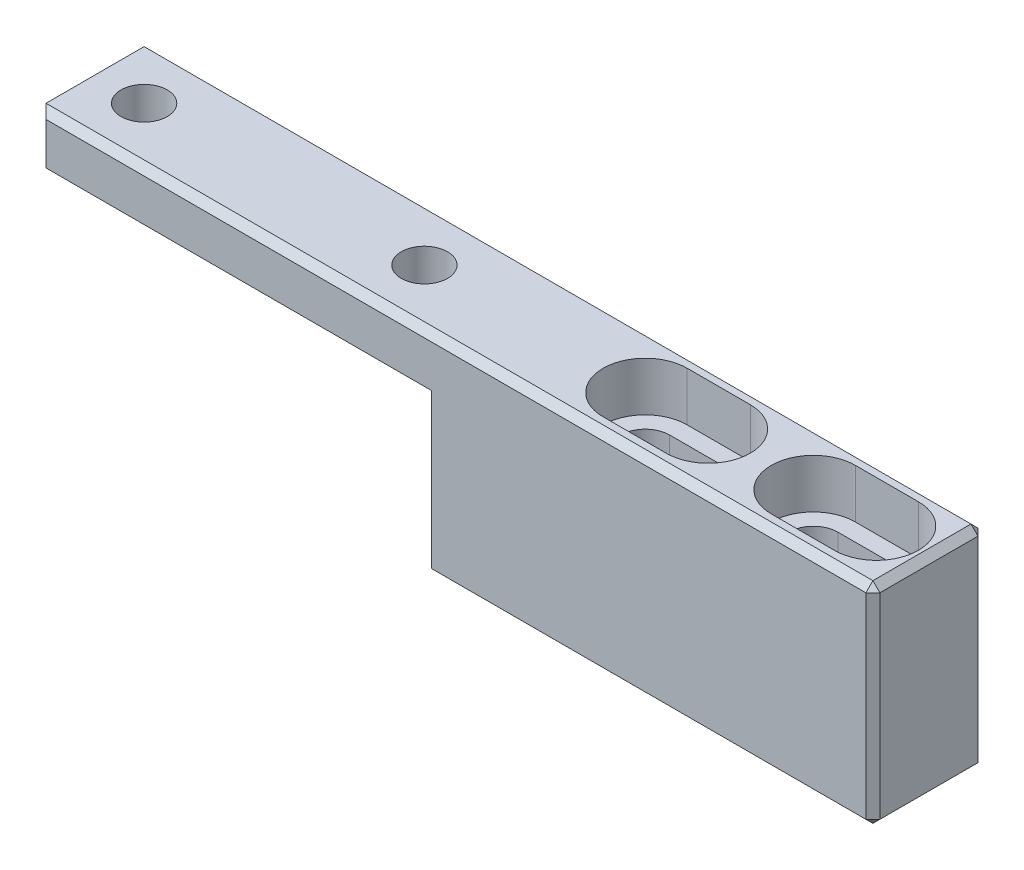
SolidWorks part; units mm, degrees
ref_plane "前视基准面" through (0, 0, 0) normal (0, 0, 1) x (1, 0, 0)
ref_plane "上视基准面" through (0, 0, 0) normal (0, 1, 0) x (1, 0, 0)
ref_plane "右视基准面" through (0, 0, 0) normal (1, 0, 0) x (0, 0, -1)
sketch "草图1" plane through (0, 0, 0) normal (0, 0, 1) x (1, 0, 0)
  line L1 (0, 0) -> (-32, 0)
  line L2 (0, 0) -> (0, 15)
  line L3 (0, 15) -> (-60, 15)
  line L4 (-60, 11) -> (-60, 15)
  line L7 (-60, 11) -> (-32, 11)
  line L8 (-32, 0) -> (-32, 11)
  dimension "D1" = 60
  dimension "D2" = 15
  dimension "D3" = 4
  dimension "D4" = 28
extrude "凸台-拉伸1" add sketch "草图1" along normal blind 8
hole_wizard "M4 螺纹孔1" positions "草图3" profile "草图2" tap size "M4" standard "ISO" end condition through all
sketch "草图3" plane through (0, 15, 0) normal (0, 1, 0) x (-1, 0, 0)
  line L0 (0, 0) -> (60, 0) construction
  line L1 (60, 8) -> (60, 0) construction
  point P0 (56, 4)
  dimension "D1" = 4
  dimension "D2" = 4
sketch "草图2" plane through (-56, 15, 4) normal (1, 0, 0) x (0, 0, 1)
  line L0 (0, 0) -> (0, 15)
  line L1 (0, 15) -> (1.65, 15)
  line L2 (1.65, 15) -> (1.65, 0)
  line L5 (1.65, 0) -> (0, 0)
  line L11 (0, -6.35) -> (0, 107.95) construction
  dimension "通孔螺纹孔钻头直径" = 3.3
  dimension "通孔螺纹孔钻头深度" = 15
cosmetic thread "孔螺蚊线1" parameters "D2"=4
sketch "草图4" plane through (0, 15, 0) normal (0, 1, 0) x (1, 0, 0)
  line L0 (-1023, -4) -> (48977, -4) construction
  line L1 (-32, -8) -> (-32, 0) construction
  line L2 (-15.75, -4) -> (-20.25, -4) construction
  line L3 (-15.75, -7) -> (-20.25, -7)
  line L4 (-15.75, -1) -> (-20.25, -1)
  line L5 (0, -8) -> (0, 0) construction
  arc A0 (-15.75, -7) -> (-15.75, -1) centre (-15.75, -4) ccw
  arc A1 (-20.25, -1) -> (-20.25, -7) centre (-20.25, -4) ccw
  point P5 (-32, -4)
  point P7 (-18, -4)
  dimension "D1" = 3
  dimension "D2" = 4.5
  dimension "D3" = 18
extrude "切除-拉伸1" cut sketch "草图4" against normal blind 3.5
sketch "草图5" plane through (0, 11.5, 0) normal (0, 1, 0) x (1, 0, 0)
  line L8 (-20.25, -5.75) -> (-15.75, -5.75)
  line L9 (-15.75, -2.25) -> (-20.25, -2.25)
  line L10 (-20.25, -5.75) -> (-15.75, -5.75)
  line L11 (-15.75, -2.25) -> (-20.25, -2.25)
  arc A6 (-15.75, -5.75) -> (-15.75, -2.25) centre (-15.75, -4) ccw
  arc A7 (-20.25, -2.25) -> (-20.25, -5.75) centre (-20.25, -4) ccw
  arc A8 (-15.75, -5.75) -> (-15.75, -2.25) centre (-15.75, -4) ccw
  arc A9 (-20.25, -2.25) -> (-20.25, -5.75) centre (-20.25, -4) ccw
  dimension "D1" = 1.25
extrude "切除-拉伸2" cut sketch "草图5" against normal through all
pattern_linear "阵列(线性)1" count 2 spacing 12 along (1, 0, 0) of "切除-拉伸2", "切除-拉伸1"
chamfer "倒角1" distance 1 angle 45 2 edges at (-60, 13, 0) (-60, 13, 8)
chamfer "倒角2" distance 0.5 angle 45 15 edges at (0, 0, 4) (-32, 5.5, 8) (-16, 0, 8) (0, 7.5, 8) (-32, 5.5, 0) (-16, 0, 0) (0, 7.5, 0) (-29.5, 15, 0) (0, 15, 4) (-29.5, 15, 8) (-60, 11, 4) (-60, 15, 4) (-45.5, 11, 8) (-32, 0, 4) (-45.5, 11, 0)
pattern_linear "阵列(线性)2" count 2 spacing 20 along (1, 0, 0) of "M4 螺纹孔1"
